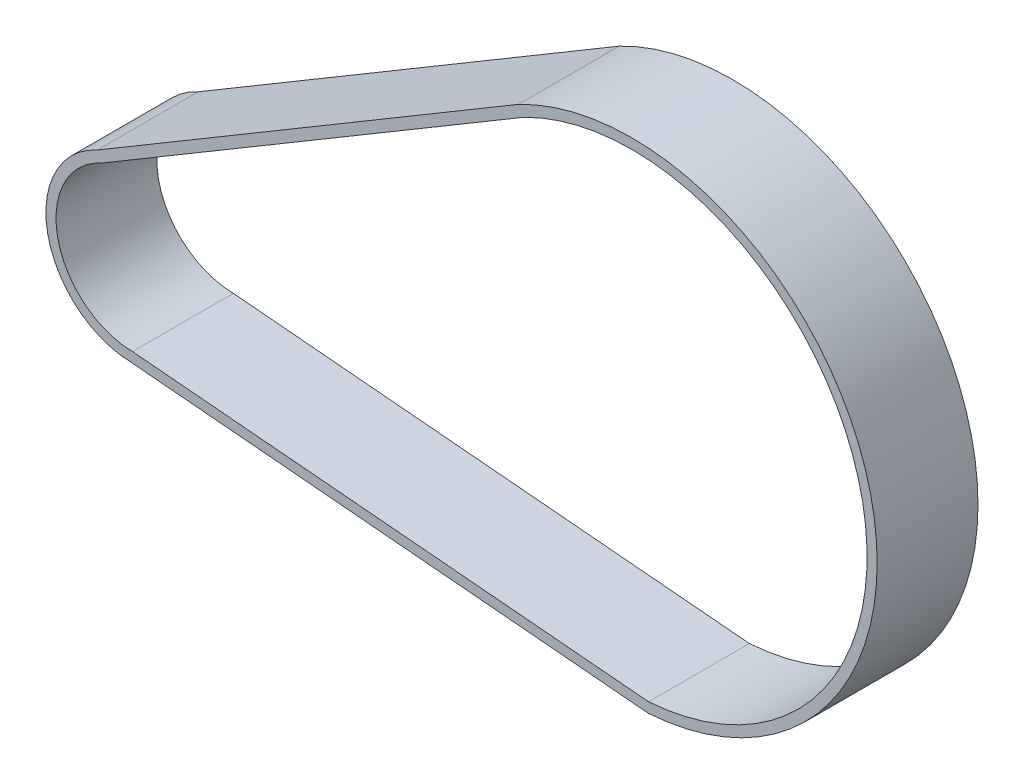
SolidWorks part; units mm, degrees
material "Rubber"
ref_plane "Front Plane" through (0, 0, 0) normal (0, 0, 1) x (1, 0, 0)
ref_plane "Top Plane" through (0, 0, 0) normal (0, 1, 0) x (1, 0, 0)
ref_plane "Right Plane" through (0, 0, 0) normal (1, 0, 0) x (0, 0, -1)
sketch "Sketch1" plane through (0, 0, 0) normal (0, 0, 1) x (1, 0, 0)
  line L0 (-4.6793, 10.505) -> (58.0099, 47.7367)
  line L5 (76.6392, -18.2322) -> (-0.1207, -11.4994)
  line L6 (-5.3721, 11.8381) -> (57.2802, 49.0479)
  line L7 (76.6258, -19.7368) -> (-0.196, -12.9985)
  arc A4 (-4.6793, 10.505) -> (-0.1207, -11.4994) centre (0, 0) ccw
  arc A5 (76.6392, -18.2322) -> (58.0099, 47.7367) centre (74.1472, 16.6789) ccw
  arc A6 (76.6258, -19.7368) -> (57.2802, 49.0479) centre (74.1472, 16.6789) ccw
  arc A7 (-5.3721, 11.8381) -> (-0.196, -12.9985) centre (0, 0) ccw
  point P6 (-0.4831, 10.9916)
  point P14 (-0.0648, -11)
  point P15 (108.1077, 24.4516)
  point P16 (91.9706, 24.9358)
  point P17 (93.0825, -20.215)
  point P18 (90.9856, 30.9882)
  point P19 (96.5411, -19.9729)
  point P20 (77.2387, 47.5717)
  point P21 (79.9559, -18.5203)
  point P22 (59.0261, 47.9803)
  point P23 (-5.3668, 10.5059)
  dimension "D1" = 76
  dimension "D2" = 35
  dimension "D3" = 11.5
  dimension "D4" = 1.5
extrude "Boss-Extrude1" add sketch "Sketch1" along normal blind 15
